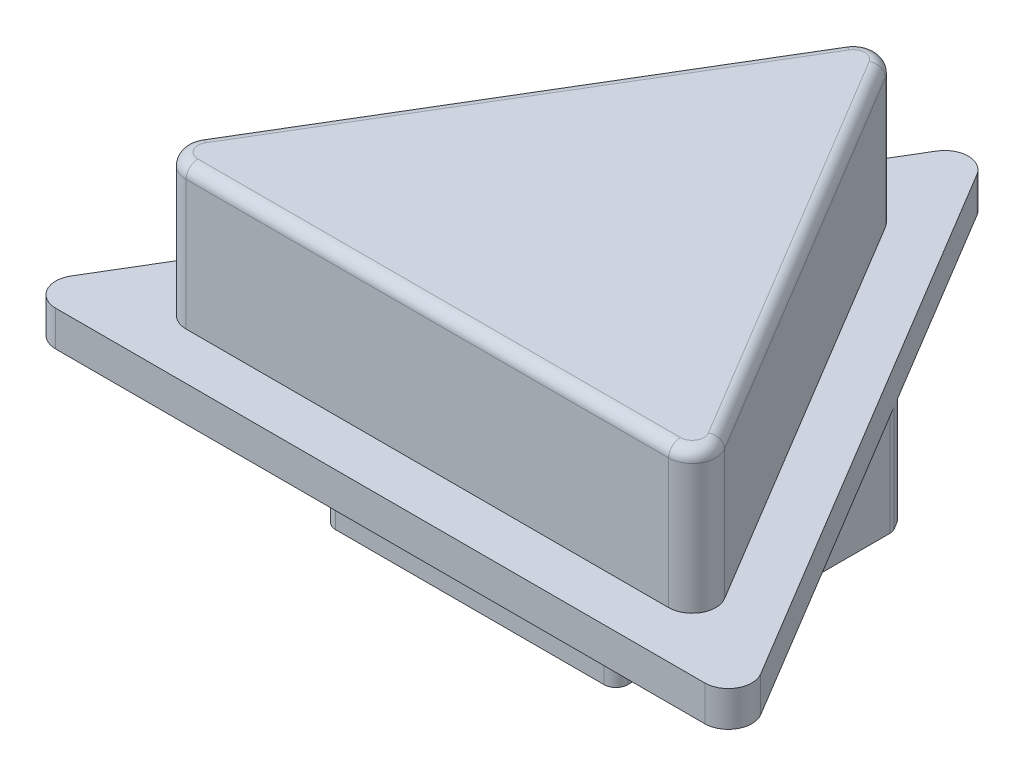
SolidWorks part; units mm, degrees
ref_plane "Front Plane" through (0, 0, 0) normal (0, 0, 1) x (1, 0, 0)
ref_plane "Top Plane" through (0, 0, 0) normal (0, 1, 0) x (1, 0, 0)
ref_plane "Right Plane" through (0, 0, 0) normal (1, 0, 0) x (0, 0, -1)
sketch "Sketch1" plane through (0, 0, 0) normal (0, 1, 0) x (1, 0, 0)
  line L0 (0, 0) -> (6, 10)
  line L1 (6, 10) -> (12, 0)
  line L2 (12, 0) -> (0, 0)
  point P3 (6, 0)
  point P5 (1.3439, 0)
  point P6 (0.5429, 0.9659)
  point P7 (10, 0)
  dimension "D1" = 12
  dimension "D2" = 10
extrude "Boss-Extrude1" add sketch "Sketch1" along normal blind 3
sketch "Sketch2" plane through (0, 0, 0) normal (0, -1, 0) x (1, 0, 0)
  line L12 (13.7662, 1) -> (-1.7662, 1)
  line L13 (-1.7662, 1) -> (6, -11.9437)
  line L14 (6, -11.9437) -> (13.7662, 1)
  line L15 (13.7662, 1) -> (-1.7662, 1)
  line L16 (-1.7662, 1) -> (6, -11.9437)
  line L17 (6, -11.9437) -> (13.7662, 1)
  point P5 (0, 0)
  point P9 (3.7855, -1.6739)
  point P10 (4.0705, -3.9615)
  dimension "D1" = 1
extrude "Boss-Extrude2" add sketch "Sketch2" along normal blind 0.75
sketch "Sketch3" plane through (0, -0.75, 0) normal (0, -1, 0) x (1, 0, 0)
  line L0 (13.7662, 1) -> (-1.7662, 1) construction
  line L1 (8.1, -1.9) -> (3.9, -1.9)
  line L2 (8.1, -1.9) -> (8.1, -6.1)
  line L3 (8.1, -6.1) -> (3.9, -6.1)
  line L4 (3.9, -1.9) -> (3.9, -6.1)
  line L5 (8.1, -1.9) -> (3.9, -6.1) construction
  line L6 (8.1, -6.1) -> (3.9, -1.9) construction
  line L7 (9.1, -7.1) -> (2.9, -7.1)
  line L8 (2.9, -0.9) -> (2.9, -7.1)
  line L9 (9.1, -0.9) -> (2.9, -0.9)
  line L10 (9.1, -0.9) -> (9.1, -7.1)
  line L11 (-1.7662, 1) -> (6, -11.9437) construction
  line L12 (6, -11.9437) -> (13.7662, 1) construction
  line L13 (-1.7662, 1) -> (6, -11.9437)
  line L14 (6, -11.9437) -> (13.7662, 1)
  point P0 (6, -4)
  point P5 (4.9051, -2.4939)
  point P8 (6, 1)
  line M1 (6, -11.9437) -> (13.7662, 1)
  line M3 (-1.7662, 1) -> (6, -11.9437)
  dimension "D1" = 4.2
  dimension "D2" = 4.2
  dimension "D4" = 5
  dimension "D3" = 1
extrude "Boss-Extrude3" add sketch "Sketch3" along normal blind 2.25 contours L10 L9 L8 L7 L4 L1 L2 L3 M3 M1 region at (6, -0.75, -7.0123)
fillet "Fillet1" radius 0.5 3 edges at (6, -0.375, -11.9437) (-1.7662, -0.375, 1) (13.7662, -0.375, 1)
fillet "Fillet2" radius 0.5 3 edges at (0, 1.5, 0) (12, 1.5, 0) (6, 1.5, -10)
fillet "Fillet4" radius 0.25 6 edges at (6, 3, -9.5282) (8.9872, 3, -5.0213) (11.552, 3, -0.2537) (6, 3, 0) (0.448, 3, -0.2537) (3.0128, 3, -5.0213)
fillet "Fillet6" radius 0.25 6 edges at (2.9, -1.875, -0.9) (2.9, -1.875, -6.777) (3.0938, -1.875, -7.1) (8.9062, -1.875, -7.1) (9.1, -1.875, -6.777) (9.1, -1.875, -0.9)
